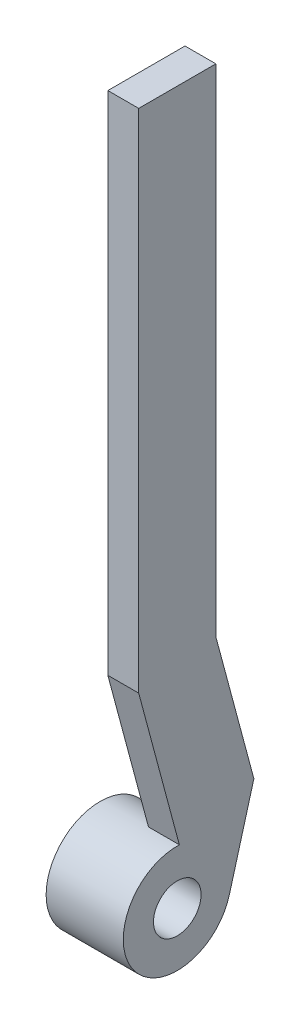
SolidWorks part; units mm, degrees
ref_plane "Front" through (0, 0, 0) normal (0, 0, 1) x (1, 0, 0)
ref_plane "Top" through (0, 0, 0) normal (0, 1, 0) x (1, 0, 0)
ref_plane "Right" through (0, 0, 0) normal (1, 0, 0) x (0, 0, -1)
sketch "Sketch1" plane through (-20.145, 0, 0) normal (-1, 0, 0) x (0, 0, 1)
  line L0 (-5, 27.967) -> (-9.926, 9.5831)
  line L1 (5, 26.6505) -> (5, 92.2879)
  line L2 (5, 92.2879) -> (-5, 92.2879)
  line L3 (-5, 92.2879) -> (-5, 27.967)
  line L4 (-0.2667, 6.9949) -> (5, 26.6505)
  line L5 (-9.926, 9.5831) -> (-6.7448, -1.8729)
  line L7 (0, 0) -> (0, 92.2879) construction
  circle A6 centre (0, 0) radius 3.0845
  arc A7 (-3.0391, 0.5274) -> (2.6861, -1.5163) centre (0, 0) ccw
  arc A8 (-3.0391, 0.5274) -> (2.6861, -1.5163) centre (0, 0) ccw construction
  circle A9 centre (0, 0) radius 7
  point P3 (0, 0)
  point P4 (-9.5755, 11.0405)
  point P10 (-11.0311, 6.0638)
  point P12 (-0.2667, 6.9949)
  dimension "D2" = 14
  dimension "D3" = 10
  dimension "D4" = 10
  dimension "D5" = 10
  dimension "D1" = 0.1
extrude "Boss-Extrude1" add sketch "Sketch1" along normal blind 10 contours A9 A6 region at (-20.145, 4.0124, -5.4925)
extrude "Boss-Extrude2" add sketch "Sketch1<3>" against normal blind 3 from surface contours A9 starting at face at (-30.145, 0, 3.0845)
sketch "Sketch1<3>" plane through (-20.145, 0, 0) normal (-1, 0, 0) x (0, 0, 1) same geometry as "Sketch1"
extrude "Boss-Extrude3" add sketch "Sketch1<5>" along normal blind 4 contours A9 L4 L1 L2 L3 L0 L5 region at (-20.145, 48.48, -0.7749)
sketch "Sketch1<5>" plane through (-20.145, 0, 0) normal (-1, 0, 0) x (0, 0, 1) same geometry as "Sketch1"
